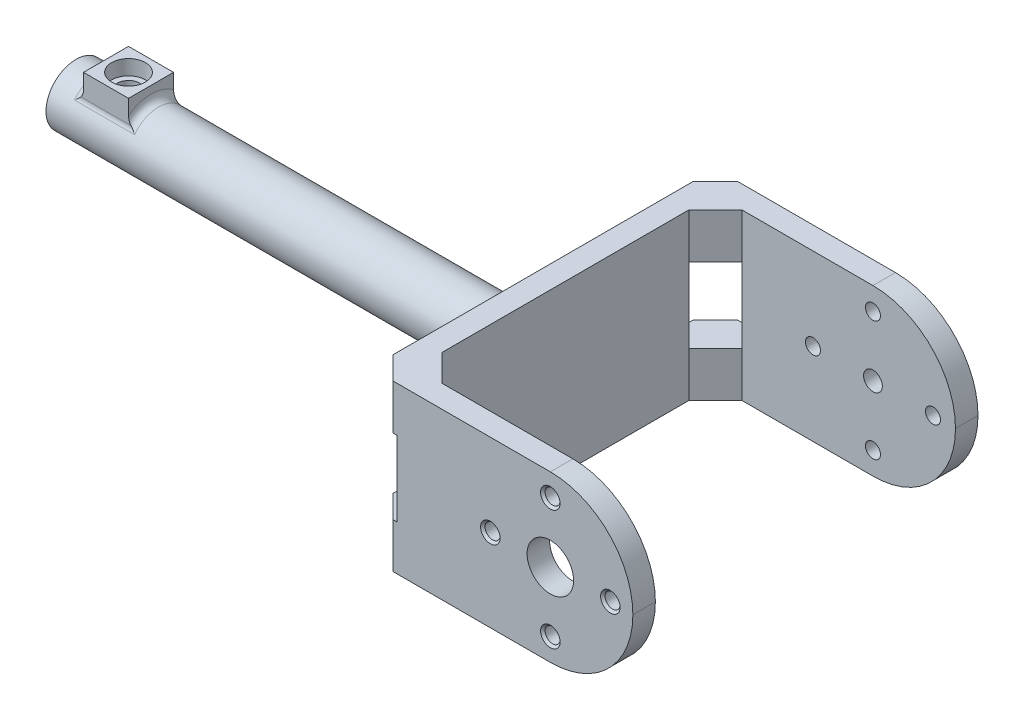
SolidWorks part; units mm, degrees
material "ABS"
ref_plane "Ön Düzlem" through (0, 0, 0) normal (0, 0, 1) x (1, 0, 0)
ref_plane "Üst Düzlem" through (0, 0, 0) normal (0, 1, 0) x (1, 0, 0)
ref_plane "Sağ Düzlem" through (0, 0, 0) normal (1, 0, 0) x (0, 0, -1)
sketch "Çizim1" plane through (0, 0, 0) normal (1, 0, 0) x (0, 0, -1)
  line L1 (-23, 11) -> (23, 11)
  line L2 (-23, 11) -> (-23, -11)
  line L3 (-23, -11) -> (23, -11)
  line L4 (23, 11) -> (23, -11)
  line L5 (-23, 11) -> (23, -11) construction
  line L6 (-23, -11) -> (23, 11) construction
  point P0 (0, 0)
  dimension "D1" = 22
  dimension "D2" = 46
extrude "Yükseklik-Ekstrüzyon1" add sketch "Çizim1" along normal blind 35
sketch "Çizim2" plane through (35, 0, 0) normal (1, 0, 0) x (0, 0, -1)
  line L0 (-23, -11) -> (23, -11) construction
  line L1 (-20, 11) -> (20, 11)
  line L2 (-20, 11) -> (-20, -11)
  line L3 (-20, -11) -> (20, -11)
  line L4 (20, 11) -> (20, -11)
  line L5 (-20, 11) -> (20, -11) construction
  line L6 (-20, -11) -> (20, 11) construction
  point P0 (0, 0)
  dimension "D1" = 40
extrude "Kes-Ekstrüzyon1" cut sketch "Çizim2" against normal blind 32
fillet "Radyus1" radius 11 4 edges at (35, -11, 21.5) (35, 11, 21.5) (35, -11, -21.5) (35, 11, -21.5)
chamfer "Pah1" distance 3 angle 45 2 edges at (0, 0, 23) (0, 0, -23)
ref_plane "Kablo Deliği Referansı" through (-10, 0, 10) normal (-0.7071, 0, 0.7071) x (0.7071, 0, 0.7071)
sketch "Çizim3" plane through (-10, 0, 10) normal (-0.7071, 0, 0.7071) x (0.7071, 0, 0.7071)
  line L1 (13.7621, 5) -> (18.7621, 5)
  line L2 (13.7621, 5) -> (13.7621, -5)
  line L3 (13.7621, -5) -> (18.7621, -5)
  line L4 (18.7621, 5) -> (18.7621, -5)
  line L5 (13.7621, 5) -> (18.7621, -5) construction
  line L6 (13.7621, -5) -> (18.7621, 5) construction
  line L7 (14.1421, 11) -> (18.3848, 11) construction
  line L8 (14.1421, -11) -> (14.1421, 11) construction
  point P0 (16.2621, 0)
  dimension "D1" = 5
  dimension "D2" = 10
  dimension "D3" = 11
  dimension "D4" = 2.12
extrude "Kes-Ekstrüzyon2" cut sketch "Çizim3" against normal blind 20
sketch "Vida Deliği Refarans" plane through (0, 0, 23) normal (0, 0, 1) x (1, 0, 0)
  circle A0 centre (24, 0) radius 8
  point P3 (32, 0)
  point P4 (24, 8)
  point P5 (16, 0)
  point P6 (24, -8)
  dimension "D1" = 8
hole_wizard "M2 Düz Başlı Makine Vidası İçin Havşa1" positions "3B Çizim1" profile "Çizim5" countersink size "M2" standard "ANSI Metrik" end condition up to next
sketch3d "3B Çizim1"
  point P0 (16, 0, 23)
  point P3 (24, 8, 23)
  point P6 (32, 0, 23)
  point P9 (24, -8, 23)
sketch "Çizim5" plane through (16, 0, 23) normal (1, 0, 0) x (0, -1, 0)
  line L0 (0, 0) -> (0, 46)
  line L1 (0, 46) -> (1, 46)
  line L2 (1, 46) -> (1, 0.3)
  line L3 (1, 0.3) -> (1.3, 0)
  line L5 (1.3, 0) -> (0, 0)
  line L6 (-1, 0.3) -> (-1.3, 0) construction
  line L11 (0, -6.35) -> (0, 107.95) construction
  dimension "Thru Hole Dia." = 2
  dimension "Thru Hole Depth" = 46
  dimension "Near C'Sink Dia." = 2.6
  dimension "Near C'Sink Angle" = 90
mirror "Aynalama2" about plane through (0, 0, 0) normal (0, 0, 1) of "M2 Düz Başlı Makine Vidası İçin Havşa1", "Kes-Ekstrüzyon2"
sketch "Çizim8" plane through (0, -5, 0) normal (0, 1, 0) x (1, 0, 0)
  line L0 (6.5337, 20) -> (3, 16.4626)
rib "Feder5" sketch "Çizim8" sketch "Çizim8" thickness 6 extrusion direction parallel to sketch draft on no parameters "D1"=6
mirror "Aynalama3" about plane through (0, 0, 0) normal (0, 1, 0) of "Feder5"
mirror "Aynalama4" about plane through (0, 0, 0) normal (0, 0, 1) of "Aynalama3", "Feder5"
sketch "Çizim10" plane through (0, 0, -23) normal (0, 0, -1) x (-1, 0, 0)
  circle A0 centre (-24, 0) radius 3.1
  dimension "D1" = 6.2
extrude "Kes-Ekstrüzyon4" cut sketch "Çizim10" against normal through all
sketch "Çizim12" plane through (0, 0, -23) normal (0, 0, -1) x (-1, 0, 0)
  circle A1 centre (-24, 0) radius 3.1
  point P4 (-24, 0)
  dimension "D1" = 6.2
extrude "Yükseklik-Ekstrüzyon3" add sketch "Çizim12" against normal blind 3
hole_wizard "M3 Düz Başlı Makine Vidası İçin Havşa1" positions "3B Çizim4" profile "Çizim17" countersink size "M3" standard "ANSI Metrik"
sketch3d "3B Çizim4"
  point P0 (24, 0, -23)
sketch "Çizim17" plane through (24, 0, -23) normal (1, 0, 0) x (0, 1, 0)
  line L0 (0, 0) -> (0, 3)
  line L1 (0, 3) -> (1.25, 3)
  line L2 (1.25, 3) -> (1.25, 0.3)
  line L3 (1.25, 0.3) -> (1.55, 0)
  line L5 (1.55, 0) -> (0, 0)
  line L6 (-1.25, 0.3) -> (-1.55, 0) construction
  line L10 (0, 3) -> (-1.25, 3) construction
  line L11 (0, -6.35) -> (0, 107.95) construction
  dimension "Hole Dia." = 2.5
  dimension "Hole Depth" = 3
  dimension "Near C'Sink Dia." = 3.1
  dimension "Near C'Sink Angle" = 90
  dimension "Drill Angle" = 180
sketch "Çizim18" plane through (0, 0, 0) normal (-1, 0, 0) x (0, 0, 1)
  circle A0 centre (0, 0) radius 4
  dimension "D1" = 8
extrude "Yükseklik-Ekstrüzyon4" add sketch "Çizim18" along normal blind 62.22
sketch "Çizim19" plane through (-62.22, 0, 0) normal (-1, 0, 0) x (0, 0, 1)
  line L1 (-2, 2) -> (2, 2)
  line L2 (-2, 2) -> (-2, -2)
  line L3 (-2, -2) -> (2, -2)
  line L4 (2, 2) -> (2, -2)
  line L5 (-2, 2) -> (2, -2) construction
  line L6 (-2, -2) -> (2, 2) construction
  point P0 (0, 0)
  dimension "D1" = 4
extrude "Kes-Ekstrüzyon5" cut sketch "Çizim19" against normal blind 10
ref_plane "Düzlem1" through (0, 0, 0) normal (0, 0, 1) x (1, 0, 0)
sketch "Çizim20" plane through (0, 0, 0) normal (0, 0, 1) x (1, 0, 0)
  line L0 (-62.22, 0) -> (-52.22, 0) construction
  line L1 (-62.22, 4) -> (-62.22, -4) construction
  line L2 (-52.22, -1.75) -> (-52.22, -3.5)
  line L3 (-52.22, -3.5) -> (-53.97, -3.5)
  line L4 (-53.97, -3.5) -> (-52.22, -1.75)
  dimension "D1" = 10
  dimension "D2" = 1.75
  dimension "D3" = 3.5
revolve "Döndür1" add sketch "Çizim20" angle 360 about L0
fillet "Radyus2" radius 1 1 edges at (0, 0, -4)
ref_plane "Düzlem2" through (0, 4, 0) normal (0, 1, 0) x (1, 0, 0)
sketch "Çizim21" plane through (0, 4, 0) normal (0, 1, 0) x (1, 0, 0)
  line L0 (-62.22, 4) -> (-62.22, -4) construction
  line L1 (-58.22, 3) -> (-52.22, 3)
  line L2 (-58.22, 3) -> (-58.22, -3)
  line L3 (-58.22, -3) -> (-52.22, -3)
  line L4 (-52.22, 3) -> (-52.22, -3)
  line L5 (-58.22, 3) -> (-52.22, -3) construction
  line L6 (-58.22, -3) -> (-52.22, 3) construction
  point P0 (-55.22, 0)
  point P5 (0, 0)
  dimension "D1" = 6
  dimension "D2" = 7
extrude "Yükseklik-Ekstrüzyon5" add sketch "Çizim21" against normal blind 2 and the other way blind 2
sketch "Çizim22" plane through (0, 6, 0) normal (0, 1, 0) x (1, 0, 0)
  line L0 (-52.22, 3) -> (-58.22, 3) construction
  circle A0 centre (-55.22, 0) radius 1.5
  point P2 (0, 0)
  point P4 (0, 0)
  point P7 (-55.22, 3)
  dimension "D1" = 3
extrude "Kes-Ekstrüzyon6" cut sketch "Çizim22" against normal blind 9
sketch "Çizim23" plane through (0, 6, 0) normal (0, 1, 0) x (1, 0, 0)
  circle A0 centre (-55.22, 0) radius 2.2514
  dimension "D1" = 4.5027
extrude "Kes-Ekstrüzyon7" cut sketch "Çizim23" against normal blind 2
fillet "Radyus3" radius 1 4 edges at (-55.22, 2.6458, -3) (-52.22, 4, 0) (-58.22, 4, 0) (-55.22, 2.6458, 3)
ref_plane "Düzlem3" through (0, -4, 0) normal (0, 1, 0) x (1, 0, 0)
sketch "Vida Ref" plane through (0, -4, 0) normal (0, 1, 0) x (1, 0, 0)
  point P0 (-55.22, 0)
hole_wizard "M2 Düz Başlı Makine Vidası İçin Havşa2" positions "Çizim29" profile "Çizim30" countersink size "M2" standard "ANSI Metrik"
sketch "Çizim29" plane through (0, -4, 0) normal (0, 1, 0) x (1, 0, 0)
  point P0 (-55.22, 0)
sketch "Çizim30" plane through (-55.22, -4, 0) normal (1, 0, 0) x (0, 0, -1)
  line L0 (0, 0) -> (0, 46.6009)
  line L1 (0, 46.6009) -> (1, 46)
  line L2 (1, 46) -> (1, 1.2)
  line L3 (1, 1.2) -> (2.2, 0)
  line L5 (2.2, 0) -> (0, 0)
  line L6 (-1, 1.2) -> (-2.2, 0) construction
  line L10 (0, 46.6009) -> (-1, 46) construction
  line L11 (0, -6.35) -> (0, 107.95) construction
  dimension "Hole Dia." = 2
  dimension "Hole Depth" = 46
  dimension "Near C'Sink Dia." = 4.4
  dimension "Near C'Sink Angle" = 90
  dimension "Drill Angle" = 118
